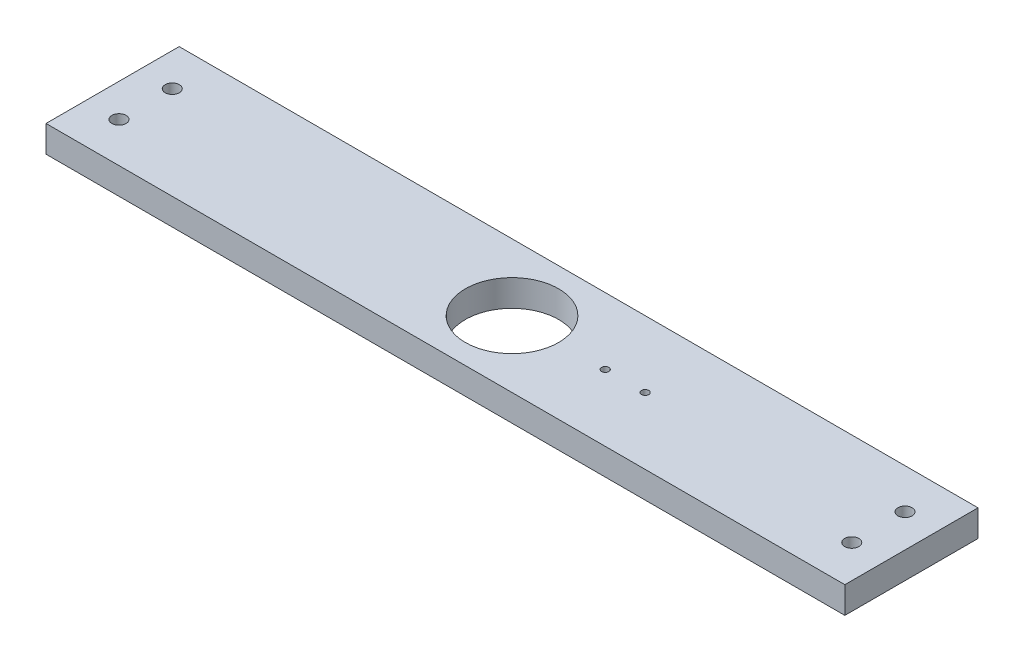
SolidWorks part; units mm, degrees
material "6061-T6 (SS)"
ref_plane "Front Plane" through (0, 0, 0) normal (0, 0, 1) x (1, 0, 0)
ref_plane "Top Plane" through (0, 0, 0) normal (0, 1, 0) x (1, 0, 0)
ref_plane "Right Plane" through (0, 0, 0) normal (1, 0, 0) x (0, 0, -1)
sketch "Sketch1" plane through (0, 0, 0) normal (0, 1, 0) x (1, 0, 0)
  line L1 (-190.5, -31.75) -> (190.5, -31.75)
  line L2 (-190.5, -31.75) -> (-190.5, 31.75)
  line L3 (-190.5, 31.75) -> (190.5, 31.75)
  line L4 (190.5, -31.75) -> (190.5, 31.75)
  line L5 (-190.5, -31.75) -> (190.5, 31.75) construction
  line L6 (-190.5, 31.75) -> (190.5, -31.75) construction
  point P0 (0, 0)
  dimension "D1" = 381
  dimension "D2" = 63.5
extrude "Boss-Extrude1" add sketch "Sketch1" along normal blind 12.7
sketch "Sketch2" plane through (0, 12.7, 0) normal (0, 1, 0) x (1, 0, 0)
  circle A0 centre (0, 0) radius 22.225
  dimension "D1" = 44.45
extrude "Cut-Extrude1" cut sketch "Sketch2" against normal through all
hole_wizard "1/4 Clearance Hole1" positions "Sketch4" profile "Sketch5" hole size "1/4" standard "ANSI Inch" end condition through all
sketch "Sketch4" plane through (0, 12.7, 0) normal (0, 1, 0) x (1, 0, 0)
  line L6 (-174.7388, -12.7) -> (-190.5, -31.75)
  line L9 (-174.7388, 12.7) -> (-190.5, 31.75)
  line L14 (190.5, 31.75) -> (174.7388, 12.7)
  line L17 (174.7388, -12.7) -> (190.5, -31.75)
  point P0 (-174.7388, 12.7)
  point P2 (174.7388, 12.7)
  point P24 (-174.7388, -12.7)
  point P26 (174.7388, -12.7)
  dimension "D1" = 349.4776
  dimension "D2" = 25.4
sketch "Sketch5" plane through (-174.7388, 12.7, -12.7) normal (1, 0, 0) x (0, 0, 1)
  line L0 (0, 0) -> (0, 12.7)
  line L1 (0, 12.7) -> (3.3782, 12.7)
  line L2 (3.3782, 12.7) -> (3.3782, 0)
  line L5 (3.3782, 0) -> (0, 0)
  line L11 (0, -6.35) -> (0, 107.95) construction
  dimension "Thru Hole Dia." = 6.7564
  dimension "Thru Hole Depth" = 12.7
hole_wizard "#8-32 Tapped Hole1" positions "Sketch6" profile "Sketch7" tap size "#8-32" standard "ANSI Inch" end condition through all
sketch "Sketch6" plane through (0, 12.7, 0) normal (0, 1, 0) x (1, 0, 0)
  point P0 (63.5, 0)
  point P2 (44.45, 0)
  point P8 (67.4285, 0)
  dimension "D1" = 44.45
  dimension "D2" = 19.05
sketch "Sketch7" plane through (63.5, 12.7, 0) normal (1, 0, 0) x (0, 0, 1)
  line L0 (0, 0) -> (0, 12.7)
  line L1 (0, 12.7) -> (1.7272, 12.7)
  line L2 (1.7272, 12.7) -> (1.7272, 0)
  line L5 (1.7272, 0) -> (0, 0)
  line L11 (0, -6.35) -> (0, 107.95) construction
  dimension "Thru Tap Drill Dia." = 3.4544
  dimension "Thru Tap Drill Depth" = 12.7
cosmetic thread "Hole Thread1" parameters "D2"=4.1656
cosmetic thread "Hole Thread2" parameters "D2"=4.1656
